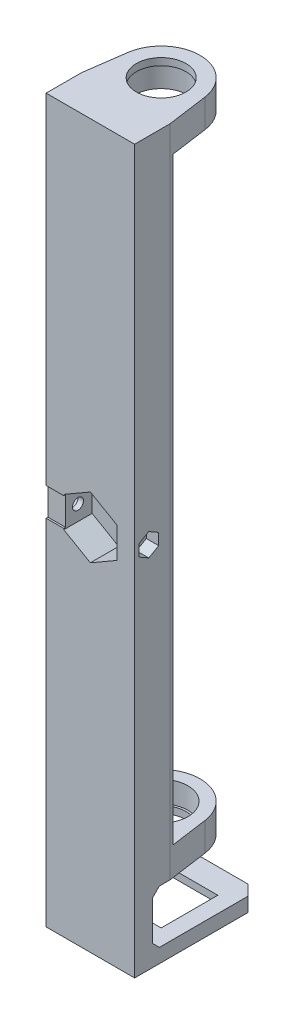
SolidWorks part; units mm, degrees
other "Markup1"
sketch "Sketch20" plane through (12.5, 200, 20) normal (0, 0.0878, 0.9961) x (0.9932, -0.1157, 0.0102)
material "ABS"
ref_plane "Front Plane" through (0, 0, 0) normal (0, 0, 1) x (1, 0, 0)
ref_plane "Top Plane" through (0, 0, 0) normal (0, 1, 0) x (1, 0, 0)
ref_plane "Right Plane" through (0, 0, 0) normal (1, 0, 0) x (0, 0, -1)
sketch "Sketch1" plane through (0, 0, 0) normal (0, 1, 0) x (1, 0, 0)
  line L0 (0, 13.844) -> (0, -25.2925) construction
  line L1 (-12.5, -10) -> (-10.8947, 1.5184)
  line L2 (-12.5, -10) -> (-12.5, -20)
  line L3 (-12.5, -20) -> (12.5, -20)
  line L4 (12.5, -10) -> (12.5, -20)
  line L5 (12.5, -10) -> (10.8947, 1.5184)
  arc A0 (10.8947, 1.5184) -> (-10.8947, 1.5184) centre (0, 0) ccw
  point P10 (0, -20)
  dimension "D1" = 22
  dimension "D2" = 25
  dimension "D3" = 10
  dimension "D4" = 10
extrude "Boss-Extrude1" add sketch "Sketch1" along normal blind 200
sketch "Sketch4" plane through (0, 0, 0) normal (0, -1, 0) x (1, 0, 0)
  circle A0 centre (0, 0) radius 7
  dimension "D1" = 14
extrude "Cut-Extrude2" cut sketch "Sketch4" against normal blind 200
sketch "Sketch3" plane through (0, 0, 0) normal (1, 0, 0) x (0, 0, -1)
  line L0 (11, 0) -> (11, 200) construction
  line L1 (11, 192) -> (-9, 192)
  line L2 (11, 192) -> (11, 23)
  line L3 (11, 23) -> (-9, 23)
  line L4 (-9, 192) -> (-9, 23)
  line L5 (11, 200) -> (1.5184, 200) construction
  line L7 (-10, 200) -> (-10, 0) construction
  line L8 (11, 0) -> (-10, 0)
  line L9 (11, 0) -> (11, 15)
  line L10 (11, 15) -> (-10, 15)
  line L11 (-10, 0) -> (-10, 15)
  dimension "D1" = 20
  dimension "D2" = 8
  dimension "D3" = 15
  dimension "D4" = 8
extrude "Cut-Extrude1" cut sketch "Sketch3" against normal mid plane 200
sketch "Sketch5" plane through (0, 192, 0) normal (0, -1, 0) x (1, 0, 0)
  circle A0 centre (0, 0) radius 7.565
  dimension "D1" = 15.13
extrude "Cut-Extrude3" cut sketch "Sketch5" against normal blind 6
sketch "Sketch6" plane through (0, 23, 0) normal (0, 1, 0) x (1, 0, 0)
  circle A0 centre (0, 0) radius 7.565
  dimension "D1" = 15.13
extrude "Cut-Extrude4" cut sketch "Sketch6" against normal blind 6
sketch "Sketch7" plane through (0, 0, 20) normal (0, 0, 1) x (1, 0, 0)
  line L0 (0, 200) -> (0, 0) construction
  line L1 (-12.5, 200) -> (12.5, 200) construction
  line L2 (-12.5, 100) -> (12.5, 100) construction
  line L3 (-12.5, 200) -> (-12.5, 0) construction
  line L4 (12.5, 200) -> (12.5, 0) construction
  circle A0 centre (0, 100) radius 4.85
  dimension "D1" = 9.7
extrude "Boss-Extrude2" [suppressed] add sketch "Sketch7" along normal blind 29 from surface
sketch "Sketch9" [suppressed] plane through (0, 0, 49) normal (0, 0, 1) x (1, 0, 0)
  circle A0 centre (0, 100) radius 2.05
  dimension "D1" = 4.1
sketch "Sketch11" plane through (0, 0, 0) normal (0, -1, 0) x (1, 0, 0)
  line L1 (0, -1000) -> (0, 49000) construction
  line L3 (-5.5, 21.5) -> (-5.5, 19.5)
  line L5 (-12.5, 20) -> (12.5, 20) construction
  line L6 (12.5, 21.5) -> (5.5, 21.5) construction
  line L7 (12.5, 21.5) -> (12.5, 19.5) construction
  line L8 (12.5, 19.5) -> (5.5, 19.5) construction
  line L9 (5.5, 21.5) -> (5.5, 19.5) construction
  line L10 (12.5, 20) -> (12.5, 10) construction
  line L11 (-12.5, 19.5) -> (-5.5, 19.5)
  line L12 (-12.5, 21.5) -> (-12.5, 19.5)
  line L13 (-12.5, 21.5) -> (-5.5, 21.5)
  dimension "D1" = 0.5
  dimension "D2" = 2
  dimension "D3" = 7
extrude "Cut-Extrude8" cut sketch "Sketch11" against normal mid plane 8 from offset 100 offset against normal yes
extrude "Cut-Extrude9" [suppressed] cut sketch "Sketch9" against normal blind 4
sketch "Sketch12" plane through (0, 0, 0) normal (0, 0, 1) x (1, 0, 0)
  line L0 (0, 104.75) -> (0, 95.25) construction
  line L1 (-4.75, 100) -> (4.75, 100) construction
  line L2 (1.3973, 101.5) -> (-1.3973, 101.5)
  line L3 (-2.6401, 97.95) -> (3.2254, 97.95) construction
  arc A2 (-1.3973, 101.5) -> (1.3973, 101.5) centre (0, 100) ccw
  dimension "D1" = 4.1
  dimension "D2" = 3.55
extrude "Cut-Extrude10" [suppressed] cut sketch "Sketch12" against normal through all both and the other way through all from surface
fillet "Fillet1" [suppressed] radius 2
sketch "Sketch13" plane through (0, 0, 0) normal (0, -1, 0) x (1, 0, 0)
  line L0 (12.5, 20) -> (12.5, 10) construction
  line L1 (-12.5, 20) -> (12.5, 20)
  line L2 (-12.5, 20) -> (-12.5, -12)
  line L3 (-9.5, -15) -> (9.5, -15)
  line L4 (12.5, 20) -> (12.5, -12)
  line L5 (-12.5, -12) -> (-9.5, -15)
  line L6 (-8, 8) -> (8, 8)
  line L7 (-8, 8) -> (-8, -8)
  line L8 (-8, -8) -> (8, -8)
  line L9 (8, 8) -> (8, -8)
  line L10 (9.5, -15) -> (12.5, -12)
  line L12 (-8.5, 8.5) -> (8.5, 8.5) construction
  line L13 (-8.5, 8.5) -> (-8.5, -8.5) construction
  line L14 (-8.5, -8.5) -> (8.5, -8.5) construction
  line L15 (8.5, 8.5) -> (8.5, -8.5) construction
  point P1 (12.5, -15)
  point P2 (-12.5, -15)
  point P11 (0, 8)
  point P13 (8, 0)
  point P22 (0, 8.5)
  point P23 (8.5, 0)
  dimension "D1" = 35
  dimension "D2" = 16
  dimension "D4" = 17
  dimension "D5" = 17
extrude "Boss-Extrude3" add sketch "Sketch13" along normal blind 4
sketch "Sketch14" plane through (-12.5, 0, 0) normal (-1, 0, 0) x (0, 0, 1)
  line L1 (15, 15) -> (10, 15)
  line L2 (15, 15) -> (15, 0)
  line L3 (15, 0) -> (10, 0)
  line L4 (10, 15) -> (10, 0)
  dimension "D1" = 5
extrude "Cut-Extrude11" cut sketch "Sketch14" against normal through all
chamfer "Chamfer1" distance 2 angle 45 2 edges at (0, 15, 15) (0, 0, 15)
sketch "Sketch15" plane through (0, -4, 0) normal (0, -1, 0) x (1, 0, 0)
  line L1 (-11.5, 11.5) -> (11.5, 11.5)
  line L2 (-11.5, 11.5) -> (-11.5, -11.5)
  line L3 (-11.5, -11.5) -> (11.5, -11.5)
  line L4 (11.5, 11.5) -> (11.5, -11.5)
  point P4 (-11.5, 0)
  point P6 (0, -11.5)
  dimension "D1" = 23
  dimension "D2" = 23
extrude "Cut-Extrude12" cut sketch "Sketch15" against normal blind 2
sketch "Sketch16" plane through (0, 0, 20) normal (0, 0, 1) x (1, 0, 0)
  line L0 (12.5, 200) -> (12.5, -4) construction
  line L1 (0, 108.6603) -> (-7.5, 104.3301)
  line L2 (-7.5, 104.3301) -> (-7.5, 95.6699)
  line L3 (-7.5, 95.6699) -> (0, 91.3397)
  line L4 (0, 91.3397) -> (7.5, 95.6699)
  line L5 (7.5, 95.6699) -> (7.5, 104.3301)
  line L6 (7.5, 104.3301) -> (0, 108.6603)
  line L7 (-12.5, 200) -> (-12.5, 104) construction
  line L8 (12.5, -4) -> (-12.5, -4) construction
  circle A0 centre (0, 100) radius 7.5 construction
  dimension "D1" = 15
  dimension "D2" = 12.5
  dimension "D3" = 104
extrude "Cut-Extrude13" cut sketch "Sketch16" against normal blind 8
sketch "Sketch17" plane through (-12.5, 0, 0) normal (-1, 0, 0) x (0, 0, 1)
  line L0 (20, -4) -> (-12, -4) construction
  line L1 (20, 200) -> (20, 104) construction
  circle A0 centre (16, 100) radius 1.55
  dimension "D2" = 3.1
  dimension "D1" = 104
  dimension "D3" = 4
extrude "Cut-Extrude14" cut sketch "Sketch17" against normal through all
sketch "Sketch18" plane through (-12.5, 0, 0) normal (-1, 0, 0) x (0, 0, 1)
  circle A0 centre (16, 100) radius 2.75
  circle A1 centre (16, 100) radius 1.55 construction
  dimension "D1" = 5.5
extrude "Cut-Extrude15" cut sketch "Sketch18" against normal blind 3.5
sketch "Sketch19" plane through (12.5, 0, 0) normal (1, 0, 0) x (0, 0, -1)
  line L0 (-9, 23) -> (-9, 192) construction
  line L1 (-16, 103.2332) -> (-18.8, 101.6166)
  line L2 (-18.8, 101.6166) -> (-18.8, 98.3834)
  line L3 (-18.8, 98.3834) -> (-16, 96.7668)
  line L4 (-16, 96.7668) -> (-13.2, 98.3834)
  line L5 (-13.2, 98.3834) -> (-13.2, 101.6166)
  line L6 (-13.2, 101.6166) -> (-16, 103.2332)
  circle A0 centre (-16, 100) radius 2.8 construction
  dimension "D1" = 5.6
extrude "Cut-Extrude16" cut sketch "Sketch19" against normal blind 3.5
fillet "Fillet2" radius 1 1 edges at (-12.5, 100, 18.75)
